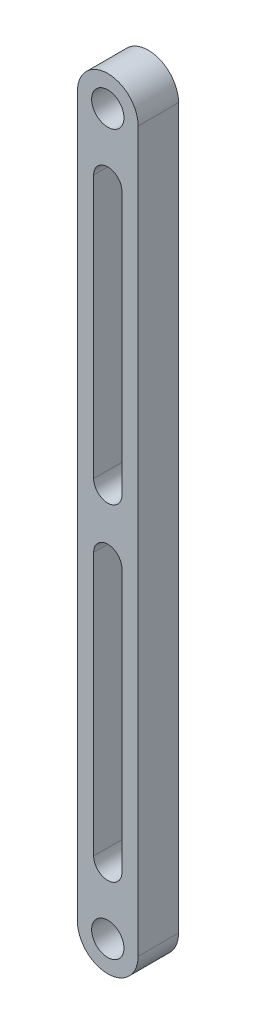
SolidWorks part; units mm, degrees
material "PEI"
ref_plane "Front Plane" through (0, 0, 0) normal (0, 0, 1) x (1, 0, 0)
ref_plane "Top Plane" through (0, 0, 0) normal (0, 1, 0) x (1, 0, 0)
ref_plane "Right Plane" through (0, 0, 0) normal (1, 0, 0) x (0, 0, -1)
sketch "Sketch1" plane through (0, 0, 0) normal (0, 0, 1) x (1, 0, 0)
  line L0 (0, -88.9) -> (0, 88.9) construction
  line L1 (-7.5, -88.9) -> (-7.5, 88.9)
  line L2 (7.5, -88.9) -> (7.5, 88.9)
  line L3 (0, -72.9) -> (0, -7.9) construction
  line L4 (-3.5, -72.9) -> (-3.5, -7.9)
  line L5 (3.5, -72.9) -> (3.5, -7.9)
  line L6 (0, 72.9) -> (0, 7.9) construction
  line L7 (3.5, 72.9) -> (3.5, 7.9)
  line L8 (-3.5, 72.9) -> (-3.5, 7.9)
  line L9 (-3.5, 40.4) -> (3.5, 40.4) construction
  line L10 (-3.5, -40.4) -> (3.5, -40.4) construction
  line L11 (-4, -88.9) -> (-3.5, -72.9) construction
  line L12 (-4, 88.9) -> (-3.5, 72.9) construction
  arc A0 (-7.5, -88.9) -> (7.5, -88.9) centre (0, -88.9) ccw
  arc A1 (7.5, 88.9) -> (-7.5, 88.9) centre (0, 88.9) ccw
  circle A2 centre (0, -88.9) radius 4
  circle A3 centre (0, 88.9) radius 4
  arc A4 (-3.5, -72.9) -> (3.5, -72.9) centre (0, -72.9) ccw
  arc A5 (3.5, -7.9) -> (-3.5, -7.9) centre (0, -7.9) ccw
  arc A6 (3.5, 72.9) -> (-3.5, 72.9) centre (0, 72.9) ccw
  arc A7 (-3.5, 7.9) -> (3.5, 7.9) centre (0, 7.9) ccw
  point P2 (0, 0)
  point P14 (0, -40.4)
  point P19 (0, 40.4)
  dimension "D3" = 8
  dimension "D1" = 177.8
  dimension "D2" = 15
  dimension "D4" = 7
  dimension "60" = 65
  dimension "D6" = 16
extrude "Boss-Extrude1" add sketch "Sketch1" along normal blind 10
